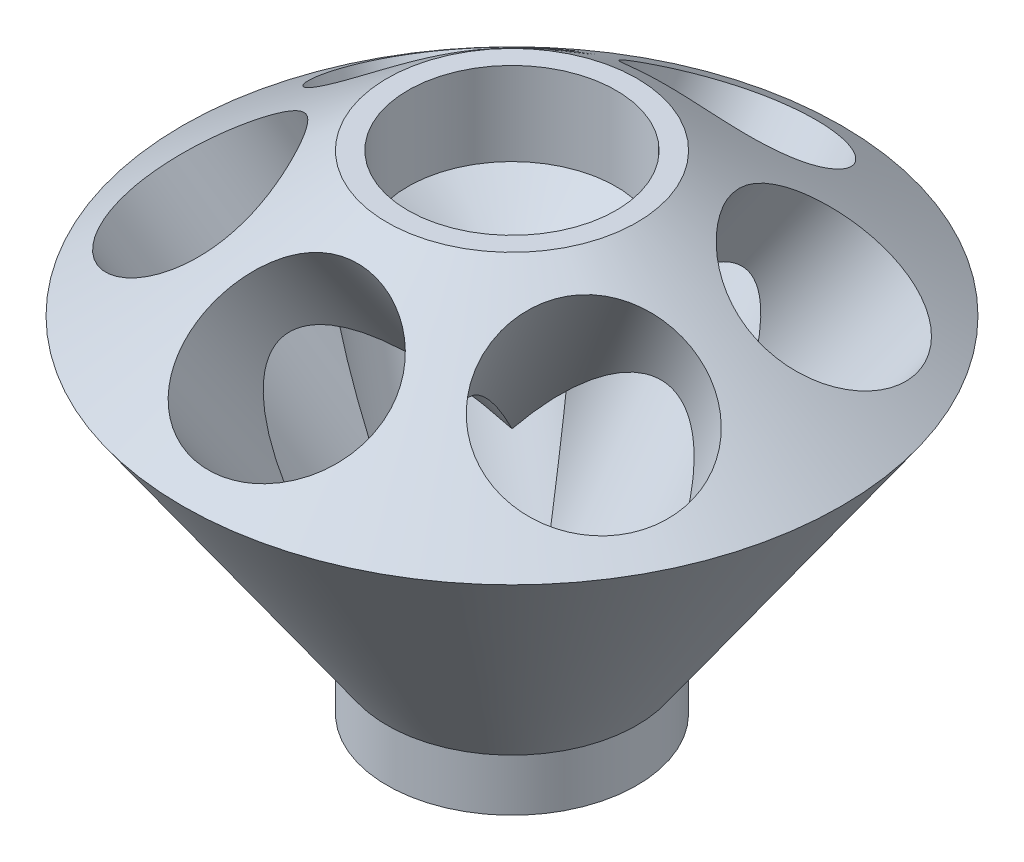
SolidWorks part; units mm, degrees
material "6061-T6 (SS)"
ref_plane "Front Plane" through (0, 0, 0) normal (0, 0, 1) x (1, 0, 0)
ref_plane "Top Plane" through (0, 0, 0) normal (0, 1, 0) x (1, 0, 0)
ref_plane "Right Plane" through (0, 0, 0) normal (1, 0, 0) x (0, 0, -1)
sketch "Sketch1" plane through (0, 0, 0) normal (0, 0, 1) x (1, 0, 0)
  line L0 (0, 0) -> (0, 26.5701)
  line L1 (0, 26.5701) -> (7.62, 26.5701)
  line L2 (7.62, 26.5701) -> (20.1039, 17.8288)
  line L3 (20.1039, 17.8288) -> (7.62, 0)
  line L5 (7.62, 26.5701) -> (20.1039, 26.5701) construction
  line L6 (0, 0) -> (0, -3.175)
  line L7 (0, -3.175) -> (7.62, -3.175)
  line L8 (7.62, -3.175) -> (7.62, 0)
  dimension "D1" = 7.62
  dimension "D2" = 7.62
  dimension "D3" = 12.4839
  dimension "D4" = 15.24
  dimension "D5" = 35
  dimension "D6" = 55
  dimension "D7" = 3.175
revolve "Revolve1" add sketch "Sketch1" angle 360 about L0
hole_wizard "7/16 (0.4375) Diameter Hole4" positions "Sketch13" profile "Sketch12" hole size "7/16" standard "ANSI Inch"
sketch "Sketch13" plane through (0.7741, -3.175, 1.4538) normal (0, -1, 0) x (-1, 0, 0)
  point P0 (0.7741, 1.4538)
sketch "Sketch12" plane through (0, -3.175, 0) normal (1, 0, 0) x (0, 0, -1)
  line L0 (0, 0) -> (0, 9.6885)
  line L1 (0, 9.6885) -> (5.5562, 6.35)
  line L2 (5.5562, 6.35) -> (5.5562, 0)
  line L5 (5.5562, 0) -> (0, 0)
  line L10 (0, 9.6885) -> (-5.5563, 6.35) construction
  line L11 (0, -6.35) -> (0, 107.95) construction
  dimension "Hole Dia." = 11.1125
  dimension "Hole Depth" = 6.35
  dimension "Drill Angle" = 118
ref_axis "Axis4" through (0, 3.175, 0) along (0, -1, 0)
hole_wizard "7/16 (0.4375) Diameter Hole5" positions "3DSketch4" profile "Sketch14" hole size "7/16" standard "ANSI Inch"
sketch3d "3DSketch4"
  line L0 (0, 22.1238, -13.97) -> (0, 22.1238, 0) construction
  line L2 (0, 3.175, 0) -> (0, -3.175, 0) construction
  circle A0 centre (0, 17.8288, 0) radius 20.1039 construction
  circle A1 centre (0, 17.8288, 0) radius 20.1039
  circle A2 centre (0, 26.5701, 0) radius 7.62 construction
  circle A3 centre (0, 26.5701, 0) radius 7.62
  point P0 (0, 22.1238, -13.97)
  point P19 (0, -2.2751, 0)
  point P21 (0, -2.2751, 0)
  point P24 (0, 18.9501, 0)
  point P26 (0, 18.9501, 0)
  dimension "D1" = 13.97
sketch "Sketch14" plane through (0, 22.1238, -13.97) normal (1, 0, 0) x (0, 0.5736, 0.8192)
  line L0 (0, 0) -> (0, 28.7385)
  line L1 (0, 28.7385) -> (5.5562, 25.4)
  line L2 (5.5562, 25.4) -> (5.5562, 0)
  line L5 (5.5562, 0) -> (0, 0)
  line L10 (0, 28.7385) -> (-5.5563, 25.4) construction
  line L11 (0, -6.35) -> (0, 107.95) construction
  dimension "Hole Dia." = 11.1125
  dimension "Hole Depth" = 25.4
  dimension "Drill Angle" = 118
pattern_circular "CirPattern3" count 6 over 360 about axis through (0, 26.5701, 0) along (0, -1, 0) of "7/16 (0.4375) Diameter Hole5"
hole_wizard "1/2 (0.5) Diameter Hole1" positions "Sketch16" profile "Sketch15" hole size "1/2" standard "ANSI Inch"
sketch "Sketch16" plane through (0, 26.5701, 0) normal (0, 1, 0) x (1, 0, 0)
  point P0 (0, 0)
sketch "Sketch15" plane through (0, 26.5701, 0) normal (1, 0, 0) x (0, 0, 1)
  line L0 (0, 0) -> (0, 8.8955)
  line L1 (0, 8.8955) -> (6.35, 5.08)
  line L2 (6.35, 5.08) -> (6.35, 0)
  line L5 (6.35, 0) -> (0, 0)
  line L10 (0, 8.8955) -> (-6.35, 5.08) construction
  line L11 (0, -6.35) -> (0, 107.95) construction
  dimension "Hole Dia." = 12.7
  dimension "Hole Depth" = 5.08
  dimension "Drill Angle" = 118
